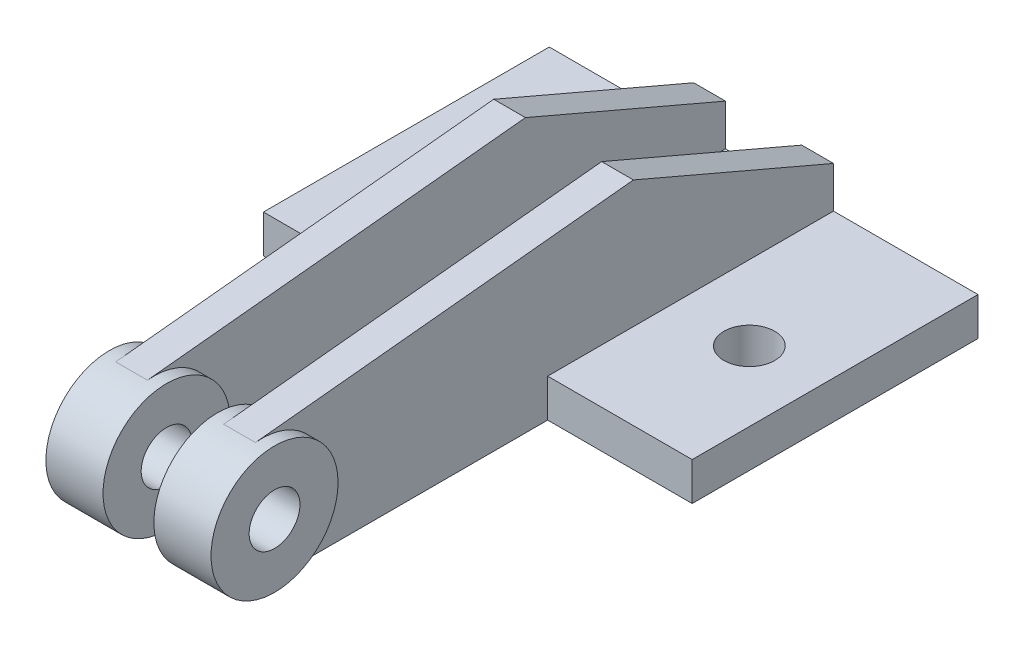
SolidWorks part; units mm, degrees
ref_plane "Front Plane" through (0, 0, 0) normal (0, 0, 1) x (1, 0, 0)
ref_plane "Top Plane" through (0, 0, 0) normal (0, 1, 0) x (1, 0, 0)
ref_plane "Right Plane" through (0, 0, 0) normal (1, 0, 0) x (0, 0, -1)
sketch "Sketch1" plane through (0, 0, 0) normal (1, 0, 0) x (0, 0, -1)
  line L1 (0, 0) -> (90, 0)
  line L2 (0, 0) -> (0, 12)
  line L3 (0, 12) -> (90, 12)
  line L4 (90, 0) -> (90, 12)
  dimension "D1" = 90
  dimension "D2" = 12
extrude "Boss-Extrude1" add sketch "Sketch1" along normal mid plane 135
sketch "Sketch2" plane through (0, 0, 0) normal (1, 0, 0) x (0, 0, -1)
  line L0 (90, 12) -> (0, 12) construction
  line L1 (90, 12) -> (0, 12)
  line L2 (90, 12) -> (90, 25)
  line L3 (90, 25) -> (27, 52)
  line L4 (27, 52) -> (-92.0232, 39.8974)
  line L5 (0, 0) -> (90, 0) construction
  line L6 (0, 12) -> (0, 0)
  line L7 (0, 0) -> (-90, 0)
  arc A0 (-92.0232, 39.8974) -> (-90, 0) centre (-90, 20) ccw
  dimension "D1" = 180
  dimension "D2" = 40
  dimension "D3" = 63
  dimension "D4" = 52
  dimension "D5" = 13
extrude "Boss-Extrude2" add sketch "Sketch2" along normal blind 10 from offset 12
sketch "Sketch3" plane through (22, 0, 0) normal (1, 0, 0) x (0, 0, -1)
  circle A0 centre (-90, 20) radius 20
  arc A1 (-92.0232, 39.8974) -> (-90, 0) centre (-90, 20) ccw construction
extrude "Boss-Extrude3" add sketch "Sketch3" along normal blind 4 and the other way blind 14
mirror "Mirror1" about plane through (0, 0, 0) normal (1, 0, 0) of "Boss-Extrude2", "Boss-Extrude3"
hole_wizard "Hole1" positions "Sketch4" profile "Sketch5" legacy end condition through all
sketch "Sketch4" plane through (26, 0, 0) normal (1, 0, 0) x (0, 0, -1)
  point P0 (-90, 20)
sketch "Sketch5" plane through (26, 20, 90) normal (0, 1, 0) x (0, 0, -1)
  line L0 (0, 0) -> (0, 93.5)
  line L1 (0, 93.5) -> (8, 93.5)
  line L2 (8, 93.5) -> (8, 0)
  line L3 (8, 0) -> (0, 0)
  line L4 (0, 110) -> (0, -10) construction
  dimension "Diameter" = 16
  dimension "Depth" = 93.5
hole_wizard "Hole2" positions "Sketch6" profile "Sketch7" legacy end condition through all
sketch "Sketch6" plane through (0, 12, 0) normal (0, 1, 0) x (1, 0, 0)
  line L0 (67.5, 0) -> (22, 0) construction
  line L1 (67.5, 90) -> (67.5, 0) construction
  point P0 (45.5, 40)
  dimension "D1" = 40
  dimension "D2" = 22
sketch "Sketch7" plane through (45.5, 12, -40) normal (1, 0, 0) x (0, 0, 1)
  line L0 (0, 0) -> (0, 12)
  line L1 (0, 12) -> (8, 12)
  line L2 (8, 12) -> (8, 0)
  line L3 (8, 0) -> (0, 0)
  line L4 (0, 110) -> (0, -10) construction
  dimension "Diameter" = 16
  dimension "Depth" = 12
mirror "Mirror2" about plane through (0, 0, 0) normal (1, 0, 0) of "Hole2"
